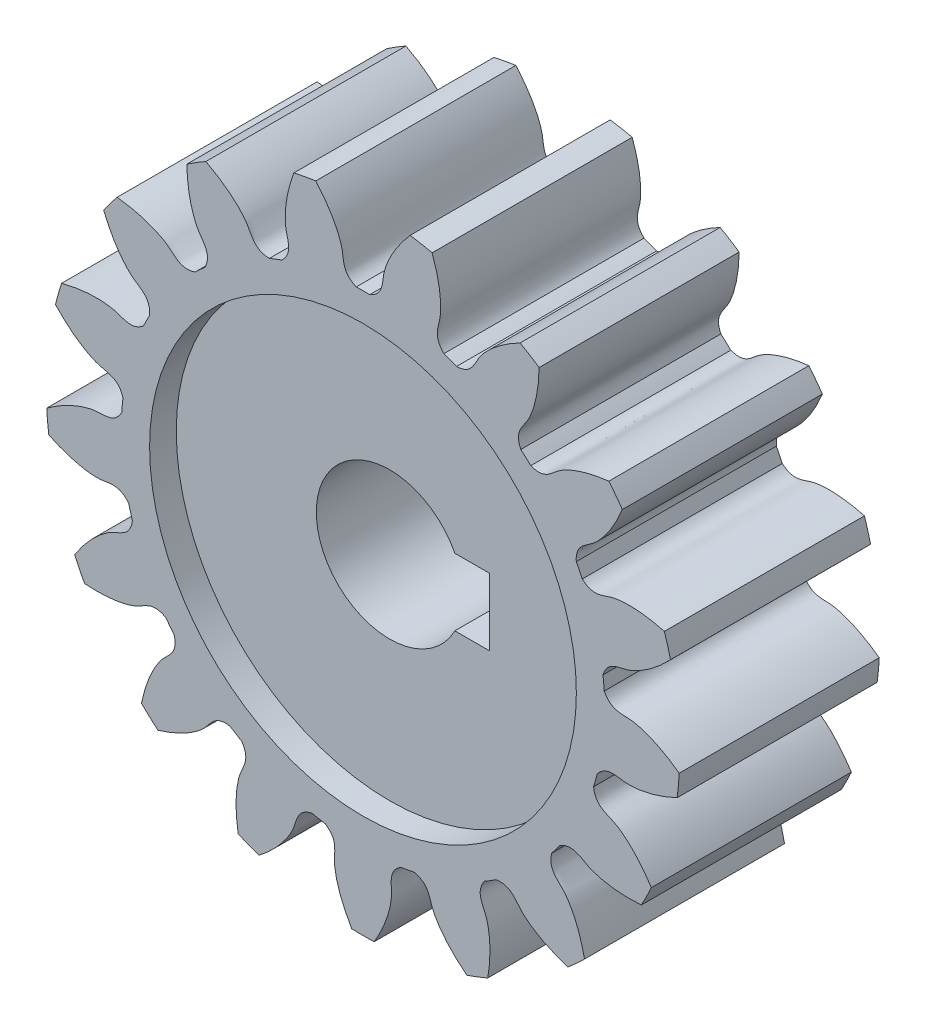
SolidWorks part; units mm, degrees
ref_plane "前视基准面" through (0, 0, 0) normal (0, 0, 1) x (1, 0, 0)
ref_plane "上视基准面" through (0, 0, 0) normal (0, 1, 0) x (1, 0, 0)
ref_plane "右视基准面" through (0, 0, 0) normal (1, 0, 0) x (0, 0, -1)
sketch "草图1" plane through (0, 0, 0) normal (0, 0, 1) x (1, 0, 0)
  circle A0 centre (0, 0) radius 23.75
extrude "凸台-拉伸1" add sketch "草图1" along normal blind 15
ref_axis "基准轴1" through (0, 0, 15) along (0, 0, -1)
sketch "草图2" plane through (0, 0, 0) normal (0, 0, 1) x (1, 0, 0)
  line L0 (0, 0) -> (0, 23.75) construction
  circle A0 centre (0, 0) radius 23.75 construction
  arc A1 (0.5042, 18.118) -> (-0.5042, 18.118) centre (0, 0) ccw
  arc A2 (7.7891, 26.8518) -> (-7.7891, 26.8518) centre (0, 0) ccw
  spline S0 degree 3 poles (0.5042, 18.118) (1.5697, 18.5621) (1.4155, 19.387) (1.5958, 20.1621) (1.6124, 20.2279) (1.6325, 20.301) (1.6564, 20.3815) (1.6842, 20.469) (1.7164, 20.5635) (1.7532, 20.6649) (1.7948, 20.773) (1.8417, 20.8876) (1.894, 21.0086) (1.952, 21.1357) (2.016, 21.2689) (2.0862, 21.408) (2.163, 21.5526) (2.2465, 21.7027) (2.337, 21.8579) (2.4348, 22.0182) (2.54, 22.1832) (2.653, 22.3527) (2.7739, 22.5264) (2.9029, 22.7042) (3.0403, 22.8857) (3.1862, 23.0708) (3.3408, 23.259) (3.5044, 23.4502) (3.6771, 23.644) (3.8591, 23.8402) (4.0505, 24.0385) (4.2515, 24.2385) (4.4622, 24.44) (4.6828, 24.6427) (4.9134, 24.8461) (5.1541, 25.0501) (5.405, 25.2543) (5.6663, 25.4584) (5.9379, 25.6619) (6.2201, 25.8647) (6.5129, 26.0663) (6.8163, 26.2664) (7.2396, 26.5336) (7.5664, 26.7263) (7.7891, 26.8518) knots 0 0 0 0 0.193883 0.199024 0.204851 0.211363 0.21856 0.226443 0.235011 0.244265 0.254205 0.264829 0.27614 0.288136 0.300817 0.314184 0.328236 0.342973 0.358397 0.374505 0.391299 0.408779 0.426944 0.445795 0.465331 0.485552 0.506459 0.528051 0.550329 0.573293 0.596941 0.621276 0.646296 0.672001 0.698392 0.725468 0.753229 0.781677 0.810809 0.840627 0.871131 0.90232 0.934195 1 1 1 1
  spline S1 degree 3 poles (-0.5042, 18.118) (-1.5697, 18.5621) (-1.4155, 19.387) (-1.5958, 20.1621) (-1.6124, 20.2279) (-1.6325, 20.301) (-1.6564, 20.3815) (-1.6842, 20.469) (-1.7164, 20.5635) (-1.7532, 20.6649) (-1.7948, 20.773) (-1.8417, 20.8876) (-1.894, 21.0086) (-1.952, 21.1357) (-2.016, 21.2689) (-2.0862, 21.408) (-2.163, 21.5526) (-2.2465, 21.7027) (-2.337, 21.8579) (-2.4348, 22.0182) (-2.54, 22.1832) (-2.653, 22.3527) (-2.7739, 22.5264) (-2.9029, 22.7042) (-3.0403, 22.8857) (-3.1862, 23.0708) (-3.3408, 23.259) (-3.5044, 23.4502) (-3.6771, 23.644) (-3.8591, 23.8402) (-4.0505, 24.0385) (-4.2515, 24.2385) (-4.4622, 24.44) (-4.6828, 24.6427) (-4.9134, 24.8461) (-5.1541, 25.0501) (-5.405, 25.2543) (-5.6663, 25.4584) (-5.9379, 25.6619) (-6.2201, 25.8647) (-6.5129, 26.0663) (-6.8163, 26.2664) (-7.2396, 26.5336) (-7.5664, 26.7263) (-7.7891, 26.8518) knots 0 0 0 0 0.193883 0.199024 0.204851 0.211363 0.21856 0.226443 0.235011 0.244265 0.254205 0.264829 0.27614 0.288136 0.300817 0.314184 0.328236 0.342973 0.358397 0.374505 0.391299 0.408779 0.426944 0.445795 0.465331 0.485552 0.506459 0.528051 0.550329 0.573293 0.596941 0.621276 0.646296 0.672001 0.698392 0.725468 0.753229 0.781677 0.810809 0.840627 0.871131 0.90232 0.934195 1 1 1 1
extrude "切除-拉伸1" cut sketch "草图2" along normal through all
pattern_circular "阵列(圆周)1" count 17 every 21.176 about axis through (0, 0, 15) along (0, 0, -1) of "切除-拉伸1"
sketch "草图3" plane through (0, 0, 0) normal (0, 0, 1) x (1, 0, 0)
  circle A0 centre (0, 0) radius 21.25 construction
  dimension "Dn" = 42.5
sketch "草图4" plane through (0, 0, 15) normal (0, 0, 1) x (1, 0, 0)
  line L1 (4.8896, 2.5184) -> (7.5, 2.5184)
  line L3 (4.8896, -2.5184) -> (7.5, -2.5184)
  line L4 (7.5, 2.5184) -> (7.5, -2.5184)
  arc A0 (4.8896, 2.5184) -> (4.8896, -2.5184) centre (0, 0) ccw
  point P3 (5.5, 0)
  dimension "D1" = 11
  dimension "D2" = 5.0367
  dimension "D3" = 7.5
extrude "切除-拉伸2" cut sketch "草图4" against normal through all
sketch "草图5" plane through (0, 0, 15) normal (0, 0, 1) x (1, 0, 0)
  circle A0 centre (0, 0) radius 16
  dimension "D1" = 32
extrude "切除-拉伸3" cut sketch "草图5" against normal blind 2
sketch "草图6" plane through (0, 0, 0) normal (0, 0, -1) x (-1, 0, 0)
  circle A0 centre (0, 0) radius 16
  dimension "D1" = 32
extrude "切除-拉伸4" cut sketch "草图6" against normal blind 2
